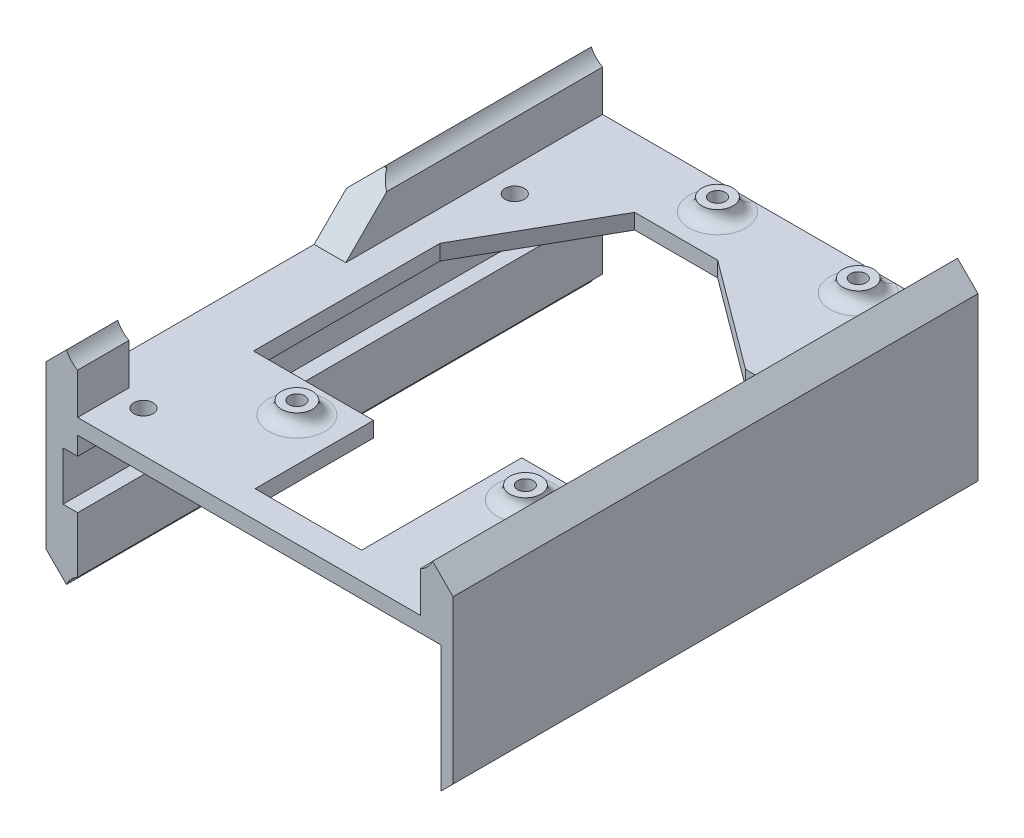
SolidWorks part; units mm, degrees
ref_plane "Front Plane" through (0, 0, 0) normal (0, 0, 1) x (1, 0, 0)
ref_plane "Top Plane" through (0, 0, 0) normal (0, 1, 0) x (1, 0, 0)
ref_plane "Right Plane" through (0, 0, 0) normal (1, 0, 0) x (0, 0, -1)
sketch "Sketch1" plane through (0, 0, 0) normal (0, 0, 1) x (1, 0, 0)
  line L0 (30.5748, -38.6095) -> (73.1149, -38.6095)
  line L1 (80.4449, -35.6839) -> (83.6448, -32.484)
  line L2 (83.6448, -32.484) -> (83.6448, -7.1349)
  line L3 (83.6448, -7.1349) -> (80.4449, -3.935)
  line L4 (73.1149, -1.0095) -> (30.5748, -1.0095)
  line L5 (23.2448, -3.935) -> (20.0448, -7.1349)
  line L6 (20.0448, -7.1349) -> (20.0448, -32.484)
  line L7 (20.0448, -32.484) -> (23.2448, -35.6839)
  line L8 (30.2818, -38.8095) -> (73.4079, -38.8095)
  line L9 (19.8448, -32.5668) -> (23.3167, -36.0387)
  line L10 (19.8448, -7.0521) -> (19.8448, -32.5668)
  line L11 (23.3167, -3.5802) -> (19.8448, -7.0521)
  line L12 (73.4079, -0.8095) -> (30.2818, -0.8095)
  line L13 (83.8448, -7.0521) -> (80.3729, -3.5802)
  line L14 (83.8448, -32.5668) -> (83.8448, -7.0521)
  line L15 (80.3729, -36.0387) -> (83.8448, -32.5668)
  line L16 (30.2818, -38.8095) -> (73.4079, -38.8095)
  line L17 (19.8448, -32.5668) -> (23.3167, -36.0387)
  line L18 (19.8448, -7.0521) -> (19.8448, -32.5668)
  line L19 (23.3167, -3.5802) -> (19.8448, -7.0521)
  line L20 (73.4079, -0.8095) -> (30.2818, -0.8095)
  line L21 (83.8448, -7.0521) -> (80.3729, -3.5802)
  line L22 (83.8448, -32.5668) -> (83.8448, -7.0521)
  line L23 (80.3729, -36.0387) -> (83.8448, -32.5668)
  arc A0 (80.4449, -35.6839) -> (73.1149, -38.6095) centre (76.8448, -37.3095) ccw
  arc A1 (73.1149, -1.0095) -> (80.4449, -3.935) centre (76.8448, -2.3095) ccw
  arc A3 (23.2448, -3.935) -> (30.5748, -1.0095) centre (26.8448, -2.3095) ccw
  arc A4 (80.3729, -36.0387) -> (73.4079, -38.8095) centre (76.8448, -37.3095) ccw
  arc A5 (30.2818, -38.8095) -> (23.3167, -36.0387) centre (26.8448, -37.3095) ccw
  arc A6 (23.3167, -3.5802) -> (30.2818, -0.8095) centre (26.8448, -2.3095) ccw
  arc A7 (73.4079, -0.8095) -> (80.3729, -3.5802) centre (76.8448, -2.3095) ccw
  arc A8 (80.3729, -36.0387) -> (73.4079, -38.8095) centre (76.8448, -37.3095) ccw
  arc A9 (30.2818, -38.8095) -> (23.3167, -36.0387) centre (26.8448, -37.3095) ccw
  arc A10 (23.3167, -3.5802) -> (30.2818, -0.8095) centre (26.8448, -2.3095) ccw
  arc A11 (73.4079, -0.8095) -> (80.3729, -3.5802) centre (76.8448, -2.3095) ccw
  arc A13 (30.5748, -38.6095) -> (23.2448, -35.6839) centre (26.8448, -37.3095) ccw
  dimension "D1" = 0
  dimension "D2" = 0.2
extrude "Boss-Extrude1" add sketch "Sketch1" against normal blind 82 contours A13 L0 A0 L1 L2 L3 A1 L4 A3 L5 L6 L7 region at (51.8448, -19.8095, 0)
sketch "Sketch2" plane through (0, -38.6095, 0) normal (0, -1, 0) x (1, 0, 0)
  line L1 (24.9892, -88.1764) -> (81.731, -88.1764)
  line L2 (24.9892, -88.1764) -> (24.9892, 2.0928)
  line L3 (24.9892, 2.0928) -> (81.731, 2.0928)
  line L4 (81.731, -88.1764) -> (81.731, 2.0928)
extrude "Cut-Extrude1" cut sketch "Sketch2" against normal blind 24
sketch "Sketch3" plane through (0, -1.0095, 0) normal (0, 1, 0) x (1, 0, 0)
  line L1 (24.9892, 82) -> (78.5389, 82)
  line L2 (24.9892, 82) -> (24.9892, -3.0245)
  line L3 (24.9892, -3.0245) -> (78.5389, -3.0245)
  line L4 (78.5389, 82) -> (78.5389, -3.0245)
extrude "Cut-Extrude2" cut sketch "Sketch3" against normal blind 11.2
sketch "Sketch7" plane through (0, -12.2095, 0) normal (0, 1, 0) x (1, 0, 0)
  line L1 (42.3691, 49.8866) -> (18.7852, 49.8866)
  line L2 (42.3691, 49.8866) -> (42.3691, 8.0085)
  line L3 (42.3691, 8.0085) -> (18.7852, 8.0085)
  line L4 (18.7852, 49.8866) -> (18.7852, 8.0085)
extrude "Cut-Extrude6" cut sketch "Sketch7" along normal through all
sketch "Sketch9" plane through (0, -12.2095, 0) normal (0, 1, 0) x (1, 0, 0)
  circle A0 centre (47.1229, 77.8184) radius 1.225
  circle A1 centre (69.1229, 77.8184) radius 1.225
  circle A2 centre (71.1229, 23.8184) radius 1.225
  circle A3 centre (24.2805, 35.2503) radius 1.225
  circle A4 centre (41.7805, 17.4607) radius 1.225
  point P14 (41.7805, 17.4477)
  dimension "D1" = 2.45
extrude "Extrude-Thin1" add sketch "Sketch9" along normal blind 2 thin contours A4 | A2 | A0 | A1 thin type one direction wall 1.2
sketch "Sketch10" plane through (0, -14.6095, 0) normal (0, -1, 0) x (1, 0, 0)
  circle A0 centre (28.8717, -6.4) radius 1.5
  circle A1 centre (77.8717, -6.4) radius 1.5
  circle A2 centre (77.8717, -64.4) radius 1.5
  circle A3 centre (28.8717, -64.4) radius 1.5
  dimension "D1" = 3
extrude "Extrude-Thin2" add sketch "Sketch10" along normal blind 2 thin thin type one direction wall 1.2
fillet "Fillet1" radius 2 8 edges at (73.5479, -12.2095, -23.8184) (44.2055, -12.2095, -17.4607) (49.5479, -12.2095, -77.8184) (71.5479, -12.2095, -77.8184) (77.8717, -14.6095, -3.7) (77.8717, -14.6095, -61.7) (28.8717, -14.6095, -3.7) (28.8717, -14.6095, -61.7)
sketch "Sketch12" plane through (0, 0, 0) normal (0, 0, 1) x (1, 0, 0)
  line L0 (25.1967, -31.6479) -> (25.1967, -16.6479) construction
  line L1 (24.9892, -25.0909) -> (22.6967, -25.0909)
  line L2 (24.9892, -25.0909) -> (24.9892, -17.4623)
  line L3 (24.9892, -17.4623) -> (22.6967, -17.4623)
  line L4 (22.6967, -25.0909) -> (22.6967, -17.4623)
  line L5 (24.9892, -14.6095) -> (24.9892, -33.8225) construction
  dimension "D1" = 2.5
extrude "Cut-Extrude7" cut sketch "Sketch12" against normal through all
sketch "Sketch13" plane through (0, -14.6095, 0) normal (0, -1, 0) x (1, 0, 0)
  circle A0 centre (77.8717, -6.4) radius 1.5 construction
  circle A1 centre (77.8717, -64.4) radius 1.5 construction
  circle A2 centre (28.8717, -64.4) radius 1.5 construction
  circle A3 centre (28.8717, -6.4) radius 1.5 construction
  circle A4 centre (77.8717, -6.4) radius 1.5
  circle A5 centre (77.8717, -64.4) radius 1.5
  circle A6 centre (28.8717, -64.4) radius 1.5
  circle A7 centre (28.8717, -6.4) radius 1.5
extrude "Cut-Extrude8" cut sketch "Sketch13" against normal through all
sketch "Sketch14" plane through (0, -12.2095, 0) normal (0, 1, 0) x (1, 0, 0)
  circle A0 centre (69.1229, 77.8184) radius 1.225 construction
  circle A1 centre (71.1229, 23.8184) radius 1.225 construction
  circle A2 centre (41.7805, 17.4607) radius 1.225 construction
  circle A4 centre (47.1229, 77.8184) radius 1.225 construction
  circle A5 centre (69.1229, 77.8184) radius 1.225
  circle A6 centre (71.1229, 23.8184) radius 1.225
  circle A7 centre (41.7805, 17.4607) radius 1.225
  circle A9 centre (47.1229, 77.8184) radius 1.225
extrude "Cut-Extrude9" cut sketch "Sketch14" against normal through all
chamfer "Chamfer1" distance 8 angle 45 1 edges at (22.517, -12.2095, -49.8866)
sketch "Sketch15" plane through (0, -12.2095, 0) normal (0, 1, 0) x (1, 0, 0)
  line L0 (29.7332, 51.8741) -> (29.7332, 22.7246)
  line L1 (29.7332, 22.7246) -> (48.4902, 22.7246)
  line L3 (65.1264, 29.2394) -> (76.9119, 29.2394)
  line L4 (76.9119, 29.2394) -> (76.9119, 58.6828)
  line L5 (76.9119, 58.6828) -> (70.6468, 58.6828)
  line L6 (70.6468, 58.6828) -> (53.7063, 71.2685)
  line L7 (53.7063, 71.2685) -> (40.7487, 71.2685)
  line L8 (40.7487, 71.2685) -> (29.7332, 51.8741)
  line L9 (48.4902, 22.7246) -> (48.4902, 4.225)
  line L10 (48.4902, 4.225) -> (65.1264, 4.225)
  line L12 (65.1264, 29.2394) -> (65.1264, 4.225)
extrude "Cut-Extrude10" cut sketch "Sketch15" against normal through all
